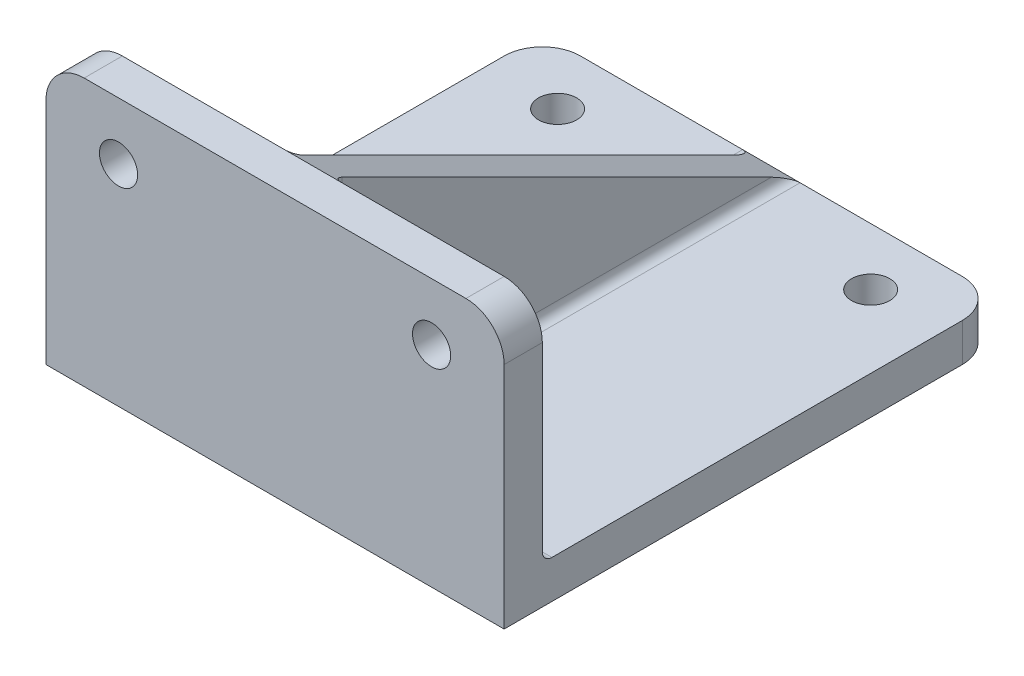
SolidWorks part; units mm, degrees
ref_plane "Front Plane" through (0, 0, 0) normal (0, 0, 1) x (1, 0, 0)
ref_plane "Top Plane" through (0, 0, 0) normal (0, 1, 0) x (1, 0, 0)
ref_plane "Right Plane" through (0, 0, 0) normal (1, 0, 0) x (0, 0, -1)
sketch "Sketch1" plane through (0, 0, 0) normal (1, 0, 0) x (0, 0, -1)
  line L0 (76.2, 0) -> (0, 0)
  line L1 (0, 0) -> (0, 38.1)
  dimension "D1" = 38.1
  dimension "D2" = 76.2
extrude "Extrude-Thin1" add sketch "Sketch1" along normal blind 76.2 thin thin type one direction reverse wall 6.35
fillet "Fillet1" radius 6.35 4 edges at (0, -3.175, -76.2) (76.2, -3.175, -76.2) (0, 38.1, 3.175) (76.2, 38.1, 3.175)
sketch "Sketch2" plane through (0, 0, 0) normal (0, 0, 1) x (1, 0, 0)
  line L0 (38.1, 38.1) -> (38.1, 14.1176) construction
  line L1 (69.85, 38.1) -> (6.35, 38.1) construction
  circle A0 centre (12.065, 28.575) radius 3.175
  circle A1 centre (64.135, 28.575) radius 3.175
  dimension "D1" = 28.575
  dimension "D2" = 12.065
  dimension "diameter" = 6.35
extrude "Cut-Extrude1" cut sketch "Sketch2" along normal blind 76.2
sketch "Sketch3" plane through (0, 0, 0) normal (0, 1, 0) x (1, 0, 0)
  line L0 (38.1, 76.2) -> (38.1, 69.3298) construction
  line L1 (69.85, 76.2) -> (6.35, 76.2) construction
  circle A0 centre (12.065, 66.675) radius 3.175
  circle A1 centre (64.135, 66.675) radius 3.175
  dimension "D1" = 6.35
  dimension "D2" = 66.675
  dimension "D3" = 12.065
extrude "Cut-Extrude2" cut sketch "Sketch3" against normal through all
ref_plane "Plane1" through (0, 30.48, -15.24) normal (0, -0.8944, 0.4472) x (1, 0, 0)
sketch "Sketch4" plane through (0, 30.48, -15.24) normal (0, -0.8944, 0.4472) x (1, 0, 0)
  line L0 (38.1, -68.1554) -> (38.1, 17.0388) construction
  line L1 (69.85, -68.1554) -> (6.35, -68.1554) construction
  line L2 (69.85, 17.0388) -> (6.35, 17.0388) construction
  line L4 (34.925, -68.1554) -> (41.275, -68.1554)
  line L5 (34.925, -68.1554) -> (34.925, 17.0388)
  line L6 (34.925, 17.0388) -> (41.275, 17.0388)
  line L7 (41.275, -68.1554) -> (41.275, 17.0388)
  line L8 (34.925, -68.1554) -> (41.275, 17.0388) construction
  line L9 (34.925, 17.0388) -> (41.275, -68.1554) construction
  point P6 (38.1, -25.5583)
  dimension "thickness" = 6.35
extrude "Boss-Extrude1" add sketch "Sketch4" along normal up to next
fillet "Fillet2" radius 1.6002 6 edges at (58.7375, 0, 0) (41.275, 0, -38.1) (41.275, 19.05, 0) (17.4625, 0, 0) (34.925, 0, -38.1) (34.925, 19.05, 0)
equation "\"D2@Sketch1\" = \"D1@Sketch1\"*2"
equation "\"D1@Extrude-Thin1\" = \"D1@Sketch1\"*2"
equation "\"D1@Sketch2\" = \"D1@Sketch1\"*.75"
equation "\"D2@Sketch3\" = \"D2@Sketch1\"*.875"
